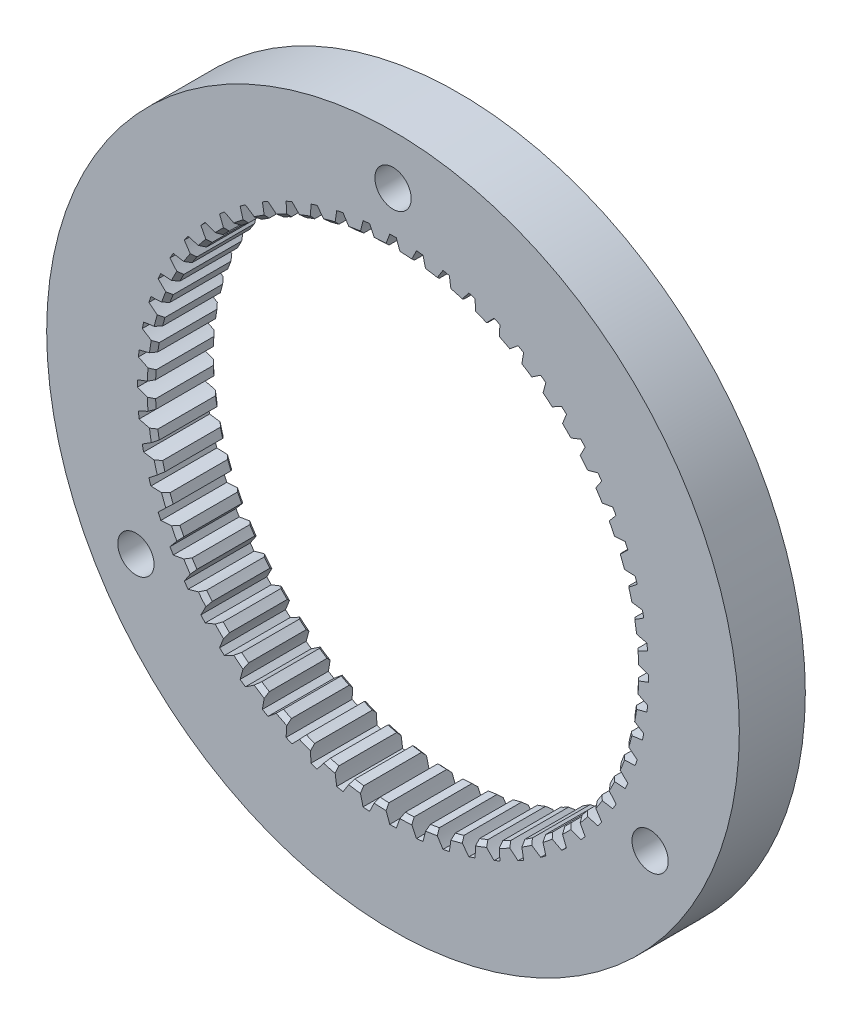
SolidWorks part; units mm, degrees
material "Plain Carbon Steel"
ref_plane "Front Plane" through (0, 0, 0) normal (0, 0, 1) x (1, 0, 0)
ref_plane "Top Plane" through (0, 0, 0) normal (0, 1, 0) x (1, 0, 0)
ref_plane "Right Plane" through (0, 0, 0) normal (1, 0, 0) x (0, 0, -1)
sketch "Model" plane through (0, 0, 0) normal (0, 0, 1) x (1, 0, 0)
  arc A1 (14.6125, -1.0371) -> (14.6408, -0.496) centre (0, 0) ccw
  arc A2 (15.3934, -1.8154) -> (15.4344, -1.4248) centre (0, 0) ccw
  arc A3 (14.424, -2.5588) -> (14.5088, -2.0237) centre (0, 0) ccw
  arc A4 (15.1193, -3.4145) -> (15.2009, -3.0303) centre (0, 0) ccw
  arc A5 (14.0775, -4.0525) -> (14.2178, -3.5292) centre (0, 0) ccw
  arc A6 (14.6796, -4.9762) -> (14.8009, -4.6026) centre (0, 0) ccw
  arc A7 (13.5768, -5.5018) -> (13.771, -4.996) centre (0, 0) ccw
  arc A8 (14.079, -6.4833) -> (14.2387, -6.1245) centre (0, 0) ccw
  arc A9 (12.9273, -6.8908) -> (13.1733, -6.4081) centre (0, 0) ccw
  arc A10 (13.3242, -7.9195) -> (13.5205, -7.5793) centre (0, 0) ccw
  arc A11 (12.1362, -8.2044) -> (12.4313, -7.75) centre (0, 0) ccw
  arc A12 (12.4234, -9.2688) -> (12.6542, -8.9511) centre (0, 0) ccw
  arc A13 (11.2122, -9.428) -> (11.5531, -9.007) centre (0, 0) ccw
  arc A14 (11.3865, -10.5167) -> (11.6493, -10.2248) centre (0, 0) ccw
  arc A15 (10.1652, -10.5484) -> (10.5484, -10.1652) centre (0, 0) ccw
  arc A16 (10.2248, -11.6493) -> (10.5167, -11.3865) centre (0, 0) ccw
  arc A17 (9.007, -11.5531) -> (9.428, -11.2122) centre (0, 0) ccw
  arc A18 (8.9511, -12.6542) -> (9.2688, -12.4234) centre (0, 0) ccw
  arc A19 (7.75, -12.4313) -> (8.2044, -12.1362) centre (0, 0) ccw
  arc A20 (7.5793, -13.5205) -> (7.9195, -13.3242) centre (0, 0) ccw
  arc A21 (6.4081, -13.1733) -> (6.8908, -12.9273) centre (0, 0) ccw
  arc A22 (6.1245, -14.2387) -> (6.4833, -14.079) centre (0, 0) ccw
  arc A23 (4.996, -13.771) -> (5.5018, -13.5768) centre (0, 0) ccw
  arc A24 (4.6026, -14.8009) -> (4.9762, -14.6796) centre (0, 0) ccw
  arc A25 (3.5292, -14.2178) -> (4.0525, -14.0775) centre (0, 0) ccw
  arc A26 (3.0303, -15.2009) -> (3.4145, -15.1193) centre (0, 0) ccw
  arc A27 (2.0237, -14.5088) -> (2.5588, -14.424) centre (0, 0) ccw
  arc A28 (1.4248, -15.4344) -> (1.8154, -15.3934) centre (0, 0) ccw
  arc A29 (0.496, -14.6408) -> (1.0371, -14.6125) centre (0, 0) ccw
  arc A30 (-0.1964, -15.4988) -> (0.1964, -15.4988) centre (0, 0) ccw
  arc A31 (-1.0371, -14.6125) -> (-0.496, -14.6408) centre (0, 0) ccw
  arc A32 (-1.8154, -15.3934) -> (-1.4248, -15.4344) centre (0, 0) ccw
  arc A33 (-2.5588, -14.424) -> (-2.0237, -14.5088) centre (0, 0) ccw
  arc A34 (-3.4145, -15.1193) -> (-3.0303, -15.2009) centre (0, 0) ccw
  arc A35 (-4.0525, -14.0775) -> (-3.5292, -14.2178) centre (0, 0) ccw
  arc A36 (-4.9762, -14.6796) -> (-4.6026, -14.8009) centre (0, 0) ccw
  arc A37 (-5.5018, -13.5768) -> (-4.996, -13.771) centre (0, 0) ccw
  arc A38 (-6.4833, -14.079) -> (-6.1245, -14.2387) centre (0, 0) ccw
  arc A39 (-6.8908, -12.9273) -> (-6.4081, -13.1733) centre (0, 0) ccw
  arc A40 (-7.9195, -13.3242) -> (-7.5793, -13.5205) centre (0, 0) ccw
  arc A41 (-8.2044, -12.1362) -> (-7.75, -12.4313) centre (0, 0) ccw
  arc A42 (-9.2688, -12.4234) -> (-8.9511, -12.6542) centre (0, 0) ccw
  arc A43 (-9.428, -11.2122) -> (-9.007, -11.5531) centre (0, 0) ccw
  arc A44 (-10.5167, -11.3865) -> (-10.2248, -11.6493) centre (0, 0) ccw
  arc A45 (-10.5484, -10.1652) -> (-10.1652, -10.5484) centre (0, 0) ccw
  arc A46 (-11.6493, -10.2248) -> (-11.3865, -10.5167) centre (0, 0) ccw
  arc A47 (-11.5531, -9.007) -> (-11.2122, -9.428) centre (0, 0) ccw
  arc A48 (-12.6542, -8.9511) -> (-12.4234, -9.2688) centre (0, 0) ccw
  arc A49 (-12.4313, -7.75) -> (-12.1362, -8.2044) centre (0, 0) ccw
  arc A50 (-13.5205, -7.5793) -> (-13.3242, -7.9195) centre (0, 0) ccw
  arc A51 (-13.1733, -6.4081) -> (-12.9273, -6.8908) centre (0, 0) ccw
  arc A52 (-14.2387, -6.1245) -> (-14.079, -6.4833) centre (0, 0) ccw
  arc A53 (-13.771, -4.996) -> (-13.5768, -5.5018) centre (0, 0) ccw
  arc A54 (-14.8009, -4.6026) -> (-14.6796, -4.9762) centre (0, 0) ccw
  arc A55 (-14.2178, -3.5292) -> (-14.0775, -4.0525) centre (0, 0) ccw
  arc A56 (-15.2009, -3.0303) -> (-15.1193, -3.4145) centre (0, 0) ccw
  arc A57 (-14.5088, -2.0237) -> (-14.424, -2.5588) centre (0, 0) ccw
  arc A58 (-15.4344, -1.4248) -> (-15.3934, -1.8154) centre (0, 0) ccw
  arc A59 (-14.6408, -0.496) -> (-14.6125, -1.0371) centre (0, 0) ccw
  arc A60 (-15.4988, 0.1964) -> (-15.4988, -0.1964) centre (0, 0) ccw
  arc A61 (-14.6125, 1.0371) -> (-14.6408, 0.496) centre (0, 0) ccw
  arc A62 (-15.3934, 1.8154) -> (-15.4344, 1.4248) centre (0, 0) ccw
  arc A63 (-14.424, 2.5588) -> (-14.5088, 2.0237) centre (0, 0) ccw
  arc A64 (-15.1193, 3.4145) -> (-15.2009, 3.0303) centre (0, 0) ccw
  arc A65 (-14.0775, 4.0525) -> (-14.2178, 3.5292) centre (0, 0) ccw
  arc A66 (-14.6796, 4.9762) -> (-14.8009, 4.6026) centre (0, 0) ccw
  arc A67 (-13.5768, 5.5018) -> (-13.771, 4.996) centre (0, 0) ccw
  arc A68 (-14.079, 6.4833) -> (-14.2387, 6.1245) centre (0, 0) ccw
  arc A69 (-12.9273, 6.8908) -> (-13.1733, 6.4081) centre (0, 0) ccw
  arc A70 (-13.3242, 7.9195) -> (-13.5205, 7.5793) centre (0, 0) ccw
  arc A71 (-12.1362, 8.2044) -> (-12.4313, 7.75) centre (0, 0) ccw
  arc A72 (-12.4234, 9.2688) -> (-12.6542, 8.9511) centre (0, 0) ccw
  arc A73 (-11.2122, 9.428) -> (-11.5531, 9.007) centre (0, 0) ccw
  arc A74 (-11.3865, 10.5167) -> (-11.6493, 10.2248) centre (0, 0) ccw
  arc A75 (-10.1652, 10.5484) -> (-10.5484, 10.1652) centre (0, 0) ccw
  arc A76 (-10.2248, 11.6493) -> (-10.5167, 11.3865) centre (0, 0) ccw
  arc A77 (-9.007, 11.5531) -> (-9.428, 11.2122) centre (0, 0) ccw
  arc A78 (-8.9511, 12.6542) -> (-9.2688, 12.4234) centre (0, 0) ccw
  arc A79 (-7.75, 12.4313) -> (-8.2044, 12.1362) centre (0, 0) ccw
  arc A80 (-7.5793, 13.5205) -> (-7.9195, 13.3242) centre (0, 0) ccw
  arc A81 (-6.4081, 13.1733) -> (-6.8908, 12.9273) centre (0, 0) ccw
  arc A82 (-6.1245, 14.2387) -> (-6.4833, 14.079) centre (0, 0) ccw
  arc A83 (-4.996, 13.771) -> (-5.5018, 13.5768) centre (0, 0) ccw
  arc A84 (-4.6026, 14.8009) -> (-4.9762, 14.6796) centre (0, 0) ccw
  arc A85 (-3.5292, 14.2178) -> (-4.0525, 14.0775) centre (0, 0) ccw
  arc A86 (-3.0303, 15.2009) -> (-3.4145, 15.1193) centre (0, 0) ccw
  arc A87 (-2.0237, 14.5088) -> (-2.5588, 14.424) centre (0, 0) ccw
  arc A88 (-1.4248, 15.4344) -> (-1.8154, 15.3934) centre (0, 0) ccw
  arc A89 (-0.496, 14.6408) -> (-1.0371, 14.6125) centre (0, 0) ccw
  arc A90 (0.1964, 15.4988) -> (-0.1964, 15.4988) centre (0, 0) ccw
  arc A91 (1.0371, 14.6125) -> (0.496, 14.6408) centre (0, 0) ccw
  arc A92 (1.8154, 15.3934) -> (1.4248, 15.4344) centre (0, 0) ccw
  arc A93 (2.5588, 14.424) -> (2.0237, 14.5088) centre (0, 0) ccw
  arc A94 (3.4145, 15.1193) -> (3.0303, 15.2009) centre (0, 0) ccw
  arc A95 (4.0525, 14.0775) -> (3.5292, 14.2178) centre (0, 0) ccw
  arc A96 (4.9762, 14.6796) -> (4.6026, 14.8009) centre (0, 0) ccw
  arc A97 (5.5018, 13.5768) -> (4.996, 13.771) centre (0, 0) ccw
  arc A98 (6.4833, 14.079) -> (6.1245, 14.2387) centre (0, 0) ccw
  arc A99 (6.8908, 12.9273) -> (6.4081, 13.1733) centre (0, 0) ccw
  arc A100 (7.9195, 13.3242) -> (7.5793, 13.5205) centre (0, 0) ccw
  arc A101 (8.2044, 12.1362) -> (7.75, 12.4313) centre (0, 0) ccw
  arc A102 (9.2688, 12.4234) -> (8.9511, 12.6542) centre (0, 0) ccw
  arc A103 (9.428, 11.2122) -> (9.007, 11.5531) centre (0, 0) ccw
  arc A104 (10.5167, 11.3865) -> (10.2248, 11.6493) centre (0, 0) ccw
  arc A105 (10.5484, 10.1652) -> (10.1652, 10.5484) centre (0, 0) ccw
  arc A106 (11.6493, 10.2248) -> (11.3865, 10.5167) centre (0, 0) ccw
  arc A107 (11.5531, 9.007) -> (11.2122, 9.428) centre (0, 0) ccw
  arc A108 (12.6542, 8.9511) -> (12.4234, 9.2688) centre (0, 0) ccw
  arc A109 (12.4313, 7.75) -> (12.1362, 8.2044) centre (0, 0) ccw
  arc A110 (13.5205, 7.5793) -> (13.3242, 7.9195) centre (0, 0) ccw
  arc A111 (13.1733, 6.4081) -> (12.9273, 6.8908) centre (0, 0) ccw
  arc A112 (14.2387, 6.1245) -> (14.079, 6.4833) centre (0, 0) ccw
  arc A113 (13.771, 4.996) -> (13.5768, 5.5018) centre (0, 0) ccw
  arc A114 (14.8009, 4.6026) -> (14.6796, 4.9762) centre (0, 0) ccw
  arc A115 (14.2178, 3.5292) -> (14.0775, 4.0525) centre (0, 0) ccw
  arc A116 (15.2009, 3.0303) -> (15.1193, 3.4145) centre (0, 0) ccw
  arc A117 (14.5088, 2.0237) -> (14.424, 2.5588) centre (0, 0) ccw
  arc A118 (15.4344, 1.4248) -> (15.3934, 1.8154) centre (0, 0) ccw
  arc A119 (14.6408, 0.496) -> (14.6125, 1.0371) centre (0, 0) ccw
  arc A120 (15.4988, -0.1964) -> (15.4988, 0.1964) centre (0, 0) ccw
  circle A121 centre (0, 0) radius 21
  spline S0 degree 3 poles (14.6125, -1.0371) (15.0016, -1.1948) (15.2065, -1.2939) (15.4344, -1.4248) knots 0 0 0 0 1 1 1 1
  spline S1 degree 3 poles (15.3934, -1.8154) (15.1432, -1.8959) (14.9222, -1.9503) (14.5088, -2.0237) knots 0 0 0 0 1 1 1 1
  spline S2 degree 3 poles (14.424, -2.5588) (14.7945, -2.7564) (14.988, -2.8764) (15.2009, -3.0303) knots 0 0 0 0 1 1 1 1
  spline S3 degree 3 poles (15.1193, -3.4145) (14.8621, -3.4685) (14.6366, -3.4994) (14.2178, -3.5292) knots 0 0 0 0 1 1 1 1
  spline S4 degree 3 poles (14.0775, -4.0525) (14.4253, -4.2877) (14.6052, -4.4273) (14.8009, -4.6026) knots 0 0 0 0 1 1 1 1
  spline S5 degree 3 poles (14.6796, -4.9762) (14.4181, -5.003) (14.1906, -5.0102) (13.771, -4.996) knots 0 0 0 0 1 1 1 1
  spline S6 degree 3 poles (13.5768, -5.5018) (13.8981, -5.7721) (14.0624, -5.9297) (14.2387, -6.1245) knots 0 0 0 0 1 1 1 1
  spline S7 degree 3 poles (14.079, -6.4833) (13.8162, -6.4827) (13.5892, -6.466) (13.1733, -6.4081) knots 0 0 0 0 1 1 1 1
  spline S8 degree 3 poles (12.9273, -6.8908) (13.2186, -7.1932) (13.3655, -7.3671) (13.5205, -7.5793) knots 0 0 0 0 1 1 1 1
  spline S9 degree 3 poles (13.3242, -7.9195) (13.0629, -7.8913) (12.8388, -7.8511) (12.4313, -7.75) knots 0 0 0 0 1 1 1 1
  spline S10 degree 3 poles (12.1362, -8.2044) (12.3943, -8.5355) (12.5223, -8.7238) (12.6542, -8.9511) knots 0 0 0 0 1 1 1 1
  spline S11 degree 3 poles (12.4234, -9.2688) (12.1665, -9.2136) (11.9478, -9.1501) (11.5531, -9.007) knots 0 0 0 0 1 1 1 1
  spline S12 degree 3 poles (11.2122, -9.428) (11.4342, -9.7844) (11.5418, -9.985) (11.6493, -10.2248) knots 0 0 0 0 1 1 1 1
  spline S13 degree 3 poles (11.3865, -10.5167) (11.1367, -10.4348) (10.926, -10.3489) (10.5484, -10.1652) knots 0 0 0 0 1 1 1 1
  spline S14 degree 3 poles (10.1652, -10.5484) (10.3489, -10.926) (10.4348, -11.1367) (10.5167, -11.3865) knots 0 0 0 0 1 1 1 1
  spline S15 degree 3 poles (10.2248, -11.6493) (9.985, -11.5418) (9.7844, -11.4342) (9.428, -11.2122) knots 0 0 0 0 1 1 1 1
  spline S16 degree 3 poles (9.007, -11.5531) (9.1501, -11.9478) (9.2136, -12.1665) (9.2688, -12.4234) knots 0 0 0 0 1 1 1 1
  spline S17 degree 3 poles (8.9511, -12.6542) (8.7238, -12.5223) (8.5355, -12.3943) (8.2044, -12.1362) knots 0 0 0 0 1 1 1 1
  spline S18 degree 3 poles (7.75, -12.4313) (7.8511, -12.8388) (7.8913, -13.0629) (7.9195, -13.3242) knots 0 0 0 0 1 1 1 1
  spline S19 degree 3 poles (7.5793, -13.5205) (7.3671, -13.3655) (7.1932, -13.2186) (6.8908, -12.9273) knots 0 0 0 0 1 1 1 1
  spline S20 degree 3 poles (6.4081, -13.1733) (6.466, -13.5892) (6.4827, -13.8162) (6.4833, -14.079) knots 0 0 0 0 1 1 1 1
  spline S21 degree 3 poles (6.1245, -14.2387) (5.9297, -14.0624) (5.7721, -13.8981) (5.5018, -13.5768) knots 0 0 0 0 1 1 1 1
  spline S22 degree 3 poles (4.996, -13.771) (5.0102, -14.1906) (5.003, -14.4181) (4.9762, -14.6796) knots 0 0 0 0 1 1 1 1
  spline S23 degree 3 poles (4.6026, -14.8009) (4.4273, -14.6052) (4.2877, -14.4253) (4.0525, -14.0775) knots 0 0 0 0 1 1 1 1
  spline S24 degree 3 poles (3.5292, -14.2178) (3.4994, -14.6366) (3.4685, -14.8621) (3.4145, -15.1193) knots 0 0 0 0 1 1 1 1
  spline S25 degree 3 poles (3.0303, -15.2009) (2.8764, -14.988) (2.7564, -14.7945) (2.5588, -14.424) knots 0 0 0 0 1 1 1 1
  spline S26 degree 3 poles (2.0237, -14.5088) (1.9503, -14.9222) (1.8959, -15.1432) (1.8154, -15.3934) knots 0 0 0 0 1 1 1 1
  spline S27 degree 3 poles (1.4248, -15.4344) (1.2939, -15.2065) (1.1948, -15.0016) (1.0371, -14.6125) knots 0 0 0 0 1 1 1 1
  spline S28 degree 3 poles (0.496, -14.6408) (0.3798, -15.0443) (0.3027, -15.2585) (0.1964, -15.4988) knots 0 0 0 0 1 1 1 1
  spline S29 degree 3 poles (-0.1964, -15.4988) (-0.3027, -15.2585) (-0.3798, -15.0443) (-0.496, -14.6408) knots 0 0 0 0 1 1 1 1
  spline S30 degree 3 poles (-1.0371, -14.6125) (-1.1948, -15.0016) (-1.2939, -15.2065) (-1.4248, -15.4344) knots 0 0 0 0 1 1 1 1
  spline S31 degree 3 poles (-1.8154, -15.3934) (-1.8959, -15.1432) (-1.9503, -14.9222) (-2.0237, -14.5088) knots 0 0 0 0 1 1 1 1
  spline S32 degree 3 poles (-2.5588, -14.424) (-2.7564, -14.7945) (-2.8764, -14.988) (-3.0303, -15.2009) knots 0 0 0 0 1 1 1 1
  spline S33 degree 3 poles (-3.4145, -15.1193) (-3.4685, -14.8621) (-3.4994, -14.6366) (-3.5292, -14.2178) knots 0 0 0 0 1 1 1 1
  spline S34 degree 3 poles (-4.0525, -14.0775) (-4.2877, -14.4253) (-4.4273, -14.6052) (-4.6026, -14.8009) knots 0 0 0 0 1 1 1 1
  spline S35 degree 3 poles (-4.9762, -14.6796) (-5.003, -14.4181) (-5.0102, -14.1906) (-4.996, -13.771) knots 0 0 0 0 1 1 1 1
  spline S36 degree 3 poles (-5.5018, -13.5768) (-5.7721, -13.8981) (-5.9297, -14.0624) (-6.1245, -14.2387) knots 0 0 0 0 1 1 1 1
  spline S37 degree 3 poles (-6.4833, -14.079) (-6.4827, -13.8162) (-6.466, -13.5892) (-6.4081, -13.1733) knots 0 0 0 0 1 1 1 1
  spline S38 degree 3 poles (-6.8908, -12.9273) (-7.1932, -13.2186) (-7.3671, -13.3655) (-7.5793, -13.5205) knots 0 0 0 0 1 1 1 1
  spline S39 degree 3 poles (-7.9195, -13.3242) (-7.8913, -13.0629) (-7.8511, -12.8388) (-7.75, -12.4313) knots 0 0 0 0 1 1 1 1
  spline S40 degree 3 poles (-8.2044, -12.1362) (-8.5355, -12.3943) (-8.7238, -12.5223) (-8.9511, -12.6542) knots 0 0 0 0 1 1 1 1
  spline S41 degree 3 poles (-9.2688, -12.4234) (-9.2136, -12.1665) (-9.1501, -11.9478) (-9.007, -11.5531) knots 0 0 0 0 1 1 1 1
  spline S42 degree 3 poles (-9.428, -11.2122) (-9.7844, -11.4342) (-9.985, -11.5418) (-10.2248, -11.6493) knots 0 0 0 0 1 1 1 1
  spline S43 degree 3 poles (-10.5167, -11.3865) (-10.4348, -11.1367) (-10.3489, -10.926) (-10.1652, -10.5484) knots 0 0 0 0 1 1 1 1
  spline S44 degree 3 poles (-10.5484, -10.1652) (-10.926, -10.3489) (-11.1367, -10.4348) (-11.3865, -10.5167) knots 0 0 0 0 1 1 1 1
  spline S45 degree 3 poles (-11.6493, -10.2248) (-11.5418, -9.985) (-11.4342, -9.7844) (-11.2122, -9.428) knots 0 0 0 0 1 1 1 1
  spline S46 degree 3 poles (-11.5531, -9.007) (-11.9478, -9.1501) (-12.1665, -9.2136) (-12.4234, -9.2688) knots 0 0 0 0 1 1 1 1
  spline S47 degree 3 poles (-12.6542, -8.9511) (-12.5223, -8.7238) (-12.3943, -8.5355) (-12.1362, -8.2044) knots 0 0 0 0 1 1 1 1
  spline S48 degree 3 poles (-12.4313, -7.75) (-12.8388, -7.8511) (-13.0629, -7.8913) (-13.3242, -7.9195) knots 0 0 0 0 1 1 1 1
  spline S49 degree 3 poles (-13.5205, -7.5793) (-13.3655, -7.3671) (-13.2186, -7.1932) (-12.9273, -6.8908) knots 0 0 0 0 1 1 1 1
  spline S50 degree 3 poles (-13.1733, -6.4081) (-13.5892, -6.466) (-13.8162, -6.4827) (-14.079, -6.4833) knots 0 0 0 0 1 1 1 1
  spline S51 degree 3 poles (-14.2387, -6.1245) (-14.0624, -5.9297) (-13.8981, -5.7721) (-13.5768, -5.5018) knots 0 0 0 0 1 1 1 1
  spline S52 degree 3 poles (-13.771, -4.996) (-14.1906, -5.0102) (-14.4181, -5.003) (-14.6796, -4.9762) knots 0 0 0 0 1 1 1 1
  spline S53 degree 3 poles (-14.8009, -4.6026) (-14.6052, -4.4273) (-14.4253, -4.2877) (-14.0775, -4.0525) knots 0 0 0 0 1 1 1 1
  spline S54 degree 3 poles (-14.2178, -3.5292) (-14.6366, -3.4994) (-14.8621, -3.4685) (-15.1193, -3.4145) knots 0 0 0 0 1 1 1 1
  spline S55 degree 3 poles (-15.2009, -3.0303) (-14.988, -2.8764) (-14.7945, -2.7564) (-14.424, -2.5588) knots 0 0 0 0 1 1 1 1
  spline S56 degree 3 poles (-14.5088, -2.0237) (-14.9222, -1.9503) (-15.1432, -1.8959) (-15.3934, -1.8154) knots 0 0 0 0 1 1 1 1
  spline S57 degree 3 poles (-15.4344, -1.4248) (-15.2065, -1.2939) (-15.0016, -1.1948) (-14.6125, -1.0371) knots 0 0 0 0 1 1 1 1
  spline S58 degree 3 poles (-14.6408, -0.496) (-15.0443, -0.3798) (-15.2585, -0.3027) (-15.4988, -0.1964) knots 0 0 0 0 1 1 1 1
  spline S59 degree 3 poles (-15.4988, 0.1964) (-15.2585, 0.3027) (-15.0443, 0.3798) (-14.6408, 0.496) knots 0 0 0 0 1 1 1 1
  spline S60 degree 3 poles (-14.6125, 1.0371) (-15.0016, 1.1948) (-15.2065, 1.2939) (-15.4344, 1.4248) knots 0 0 0 0 1 1 1 1
  spline S61 degree 3 poles (-15.3934, 1.8154) (-15.1432, 1.8959) (-14.9222, 1.9503) (-14.5088, 2.0237) knots 0 0 0 0 1 1 1 1
  spline S62 degree 3 poles (-14.424, 2.5588) (-14.7945, 2.7564) (-14.988, 2.8764) (-15.2009, 3.0303) knots 0 0 0 0 1 1 1 1
  spline S63 degree 3 poles (-15.1193, 3.4145) (-14.8621, 3.4685) (-14.6366, 3.4994) (-14.2178, 3.5292) knots 0 0 0 0 1 1 1 1
  spline S64 degree 3 poles (-14.0775, 4.0525) (-14.4253, 4.2877) (-14.6052, 4.4273) (-14.8009, 4.6026) knots 0 0 0 0 1 1 1 1
  spline S65 degree 3 poles (-14.6796, 4.9762) (-14.4181, 5.003) (-14.1906, 5.0102) (-13.771, 4.996) knots 0 0 0 0 1 1 1 1
  spline S66 degree 3 poles (-13.5768, 5.5018) (-13.8981, 5.7721) (-14.0624, 5.9297) (-14.2387, 6.1245) knots 0 0 0 0 1 1 1 1
  spline S67 degree 3 poles (-14.079, 6.4833) (-13.8162, 6.4827) (-13.5892, 6.466) (-13.1733, 6.4081) knots 0 0 0 0 1 1 1 1
  spline S68 degree 3 poles (-12.9273, 6.8908) (-13.2186, 7.1932) (-13.3655, 7.3671) (-13.5205, 7.5793) knots 0 0 0 0 1 1 1 1
  spline S69 degree 3 poles (-13.3242, 7.9195) (-13.0629, 7.8913) (-12.8388, 7.8511) (-12.4313, 7.75) knots 0 0 0 0 1 1 1 1
  spline S70 degree 3 poles (-12.1362, 8.2044) (-12.3943, 8.5355) (-12.5223, 8.7238) (-12.6542, 8.9511) knots 0 0 0 0 1 1 1 1
  spline S71 degree 3 poles (-12.4234, 9.2688) (-12.1665, 9.2136) (-11.9478, 9.1501) (-11.5531, 9.007) knots 0 0 0 0 1 1 1 1
  spline S72 degree 3 poles (-11.2122, 9.428) (-11.4342, 9.7844) (-11.5418, 9.985) (-11.6493, 10.2248) knots 0 0 0 0 1 1 1 1
  spline S73 degree 3 poles (-11.3865, 10.5167) (-11.1367, 10.4348) (-10.926, 10.3489) (-10.5484, 10.1652) knots 0 0 0 0 1 1 1 1
  spline S74 degree 3 poles (-10.1652, 10.5484) (-10.3489, 10.926) (-10.4348, 11.1367) (-10.5167, 11.3865) knots 0 0 0 0 1 1 1 1
  spline S75 degree 3 poles (-10.2248, 11.6493) (-9.985, 11.5418) (-9.7844, 11.4342) (-9.428, 11.2122) knots 0 0 0 0 1 1 1 1
  spline S76 degree 3 poles (-9.007, 11.5531) (-9.1501, 11.9478) (-9.2136, 12.1665) (-9.2688, 12.4234) knots 0 0 0 0 1 1 1 1
  spline S77 degree 3 poles (-8.9511, 12.6542) (-8.7238, 12.5223) (-8.5355, 12.3943) (-8.2044, 12.1362) knots 0 0 0 0 1 1 1 1
  spline S78 degree 3 poles (-7.75, 12.4313) (-7.8511, 12.8388) (-7.8913, 13.0629) (-7.9195, 13.3242) knots 0 0 0 0 1 1 1 1
  spline S79 degree 3 poles (-7.5793, 13.5205) (-7.3671, 13.3655) (-7.1932, 13.2186) (-6.8908, 12.9273) knots 0 0 0 0 1 1 1 1
  spline S80 degree 3 poles (-6.4081, 13.1733) (-6.466, 13.5892) (-6.4827, 13.8162) (-6.4833, 14.079) knots 0 0 0 0 1 1 1 1
  spline S81 degree 3 poles (-6.1245, 14.2387) (-5.9297, 14.0624) (-5.7721, 13.8981) (-5.5018, 13.5768) knots 0 0 0 0 1 1 1 1
  spline S82 degree 3 poles (-4.996, 13.771) (-5.0102, 14.1906) (-5.003, 14.4181) (-4.9762, 14.6796) knots 0 0 0 0 1 1 1 1
  spline S83 degree 3 poles (-4.6026, 14.8009) (-4.4273, 14.6052) (-4.2877, 14.4253) (-4.0525, 14.0775) knots 0 0 0 0 1 1 1 1
  spline S84 degree 3 poles (-3.5292, 14.2178) (-3.4994, 14.6366) (-3.4685, 14.8621) (-3.4145, 15.1193) knots 0 0 0 0 1 1 1 1
  spline S85 degree 3 poles (-3.0303, 15.2009) (-2.8764, 14.988) (-2.7564, 14.7945) (-2.5588, 14.424) knots 0 0 0 0 1 1 1 1
  spline S86 degree 3 poles (-2.0237, 14.5088) (-1.9503, 14.9222) (-1.8959, 15.1432) (-1.8154, 15.3934) knots 0 0 0 0 1 1 1 1
  spline S87 degree 3 poles (-1.4248, 15.4344) (-1.2939, 15.2065) (-1.1948, 15.0016) (-1.0371, 14.6125) knots 0 0 0 0 1 1 1 1
  spline S88 degree 3 poles (-0.496, 14.6408) (-0.3798, 15.0443) (-0.3027, 15.2585) (-0.1964, 15.4988) knots 0 0 0 0 1 1 1 1
  spline S89 degree 3 poles (0.1964, 15.4988) (0.3027, 15.2585) (0.3798, 15.0443) (0.496, 14.6408) knots 0 0 0 0 1 1 1 1
  spline S90 degree 3 poles (1.0371, 14.6125) (1.1948, 15.0016) (1.2939, 15.2065) (1.4248, 15.4344) knots 0 0 0 0 1 1 1 1
  spline S91 degree 3 poles (1.8154, 15.3934) (1.8959, 15.1432) (1.9503, 14.9222) (2.0237, 14.5088) knots 0 0 0 0 1 1 1 1
  spline S92 degree 3 poles (2.5588, 14.424) (2.7564, 14.7945) (2.8764, 14.988) (3.0303, 15.2009) knots 0 0 0 0 1 1 1 1
  spline S93 degree 3 poles (3.4145, 15.1193) (3.4685, 14.8621) (3.4994, 14.6366) (3.5292, 14.2178) knots 0 0 0 0 1 1 1 1
  spline S94 degree 3 poles (4.0525, 14.0775) (4.2877, 14.4253) (4.4273, 14.6052) (4.6026, 14.8009) knots 0 0 0 0 1 1 1 1
  spline S95 degree 3 poles (4.9762, 14.6796) (5.003, 14.4181) (5.0102, 14.1906) (4.996, 13.771) knots 0 0 0 0 1 1 1 1
  spline S96 degree 3 poles (5.5018, 13.5768) (5.7721, 13.8981) (5.9297, 14.0624) (6.1245, 14.2387) knots 0 0 0 0 1 1 1 1
  spline S97 degree 3 poles (6.4833, 14.079) (6.4827, 13.8162) (6.466, 13.5892) (6.4081, 13.1733) knots 0 0 0 0 1 1 1 1
  spline S98 degree 3 poles (6.8908, 12.9273) (7.1932, 13.2186) (7.3671, 13.3655) (7.5793, 13.5205) knots 0 0 0 0 1 1 1 1
  spline S99 degree 3 poles (7.9195, 13.3242) (7.8913, 13.0629) (7.8511, 12.8388) (7.75, 12.4313) knots 0 0 0 0 1 1 1 1
  spline S100 degree 3 poles (8.2044, 12.1362) (8.5355, 12.3943) (8.7238, 12.5223) (8.9511, 12.6542) knots 0 0 0 0 1 1 1 1
  spline S101 degree 3 poles (9.2688, 12.4234) (9.2136, 12.1665) (9.1501, 11.9478) (9.007, 11.5531) knots 0 0 0 0 1 1 1 1
  spline S102 degree 3 poles (9.428, 11.2122) (9.7844, 11.4342) (9.985, 11.5418) (10.2248, 11.6493) knots 0 0 0 0 1 1 1 1
  spline S103 degree 3 poles (10.5167, 11.3865) (10.4348, 11.1367) (10.3489, 10.926) (10.1652, 10.5484) knots 0 0 0 0 1 1 1 1
  spline S104 degree 3 poles (10.5484, 10.1652) (10.926, 10.3489) (11.1367, 10.4348) (11.3865, 10.5167) knots 0 0 0 0 1 1 1 1
  spline S105 degree 3 poles (11.6493, 10.2248) (11.5418, 9.985) (11.4342, 9.7844) (11.2122, 9.428) knots 0 0 0 0 1 1 1 1
  spline S106 degree 3 poles (11.5531, 9.007) (11.9478, 9.1501) (12.1665, 9.2136) (12.4234, 9.2688) knots 0 0 0 0 1 1 1 1
  spline S107 degree 3 poles (12.6542, 8.9511) (12.5223, 8.7238) (12.3943, 8.5355) (12.1362, 8.2044) knots 0 0 0 0 1 1 1 1
  spline S108 degree 3 poles (12.4313, 7.75) (12.8388, 7.8511) (13.0629, 7.8913) (13.3242, 7.9195) knots 0 0 0 0 1 1 1 1
  spline S109 degree 3 poles (13.5205, 7.5793) (13.3655, 7.3671) (13.2186, 7.1932) (12.9273, 6.8908) knots 0 0 0 0 1 1 1 1
  spline S110 degree 3 poles (13.1733, 6.4081) (13.5892, 6.466) (13.8162, 6.4827) (14.079, 6.4833) knots 0 0 0 0 1 1 1 1
  spline S111 degree 3 poles (14.2387, 6.1245) (14.0624, 5.9297) (13.8981, 5.7721) (13.5768, 5.5018) knots 0 0 0 0 1 1 1 1
  spline S112 degree 3 poles (13.771, 4.996) (14.1906, 5.0102) (14.4181, 5.003) (14.6796, 4.9762) knots 0 0 0 0 1 1 1 1
  spline S113 degree 3 poles (14.8009, 4.6026) (14.6052, 4.4273) (14.4253, 4.2877) (14.0775, 4.0525) knots 0 0 0 0 1 1 1 1
  spline S114 degree 3 poles (14.2178, 3.5292) (14.6366, 3.4994) (14.8621, 3.4685) (15.1193, 3.4145) knots 0 0 0 0 1 1 1 1
  spline S115 degree 3 poles (15.2009, 3.0303) (14.988, 2.8764) (14.7945, 2.7564) (14.424, 2.5588) knots 0 0 0 0 1 1 1 1
  spline S116 degree 3 poles (14.5088, 2.0237) (14.9222, 1.9503) (15.1432, 1.8959) (15.3934, 1.8154) knots 0 0 0 0 1 1 1 1
  spline S117 degree 3 poles (15.4344, 1.4248) (15.2065, 1.2939) (15.0016, 1.1948) (14.6125, 1.0371) knots 0 0 0 0 1 1 1 1
  spline S118 degree 3 poles (14.6408, 0.496) (15.0443, 0.3798) (15.2585, 0.3027) (15.4988, 0.1964) knots 0 0 0 0 1 1 1 1
  spline S119 degree 3 poles (15.4988, -0.1964) (15.2585, -0.3027) (15.0443, -0.3798) (14.6408, -0.496) knots 0 0 0 0 1 1 1 1
  dimension "D1" = 42
extrude "Boss-Extrude1" add sketch "Model" along normal blind 4
hole_wizard "M2 Clearance Hole1" positions "Sketch2" profile "Sketch3" hole size "M2" standard "ANSI Metric"
sketch "Sketch2" plane through (0, 0, 0) normal (0, 0, -1) x (-1, 0, 0)
  circle A0 centre (0, 0) radius 18 construction
  point P11 (0, 18)
  point P43 (15.5885, -9)
  point P45 (-15.5885, -9)
  point P50 (15.5885, 9)
  point P52 (-15.5885, 9)
  point P63 (0, -18)
  dimension "D2" = 36
  dimension "D1" = 6
sketch "Sketch3" plane through (0, 18, 0) normal (1, 0, 0) x (0, 1, 0)
  line L0 (0, 0) -> (0, 4)
  line L1 (0, 4) -> (1.1, 4)
  line L2 (1.1, 4) -> (1.1, 0.9)
  line L3 (1.1, 0.9) -> (2, 0)
  line L5 (2, 0) -> (0, 0)
  line L6 (-1.1, 0.9) -> (-2, 0) construction
  line L11 (0, -6.35) -> (0, 107.95) construction
  dimension "Thru Hole Dia." = 2.2
  dimension "Thru Hole Depth" = 4
  dimension "Near C'Sink Dia." = 4
  dimension "Near C'Sink Angle" = 90
chamfer "Chamfer1" distance 0.25 angle 45 60 edges at (12.2859, -7.9785, 0) (13.0526, -6.6506, 0) (13.6762, -5.2498, 0) (14.1501, -3.7915, 0) (14.4689, -2.2916, 0) (14.6292, -0.7667, 0) (14.6292, 0.7667, 0) (14.4689, 2.2916, 0) (14.1501, 3.7915, 0) (11.3846, -9.2191, 0) (10.3586, -10.3586, 0) (9.2191, -11.3846, 0) (6.6506, -13.0526, 0) (7.9785, -12.2859, 0) (5.2498, -13.6762, 0) (3.7915, -14.1501, 0) (2.2916, -14.4689, 0) (0.7667, -14.6292, 0) (-0.7667, -14.6292, 0) (-2.2916, -14.4689, 0) (-3.7915, -14.1501, 0) (-5.2498, -13.6762, 0) (-6.6506, -13.0526, 0) (-7.9785, -12.2859, 0) (13.6762, 5.2498, 0) (13.0526, 6.6506, 0) (-14.4689, 2.2916, 0) (-14.1501, 3.7915, 0) (-13.6762, 5.2498, 0) (-13.0526, 6.6506, 0) (-12.2859, 7.9785, 0) (-11.3846, 9.2191, 0) (-10.3586, 10.3586, 0) (-14.6292, 0.7667, 0) (-9.2191, -11.3846, 0) (-10.3586, -10.3586, 0) (-14.6292, -0.7667, 0) (-14.4689, -2.2916, 0) (-14.1501, -3.7915, 0) (-13.6762, -5.2498, 0) (-13.0526, -6.6506, 0) (-12.2859, -7.9785, 0) (-11.3846, -9.2191, 0) (-9.2191, 11.3846, 0) (-7.9785, 12.2859, 0) (-6.6506, 13.0526, 0) (-5.2498, 13.6762, 0) (-3.7915, 14.1501, 0) (-2.2916, 14.4689, 0) (-0.7667, 14.6292, 0) (0.7667, 14.6292, 0) (2.2916, 14.4689, 0) (3.7915, 14.1501, 0) (5.2498, 13.6762, 0) (6.6506, 13.0526, 0) (7.9785, 12.2859, 0) (9.2191, 11.3846, 0) (10.3586, 10.3586, 0) (11.3846, 9.2191, 0) (12.2859, 7.9785, 0)
chamfer "Chamfer2" distance 0.25 angle 45 60 edges at (-7.9785, -12.2859, 4) (-9.2191, -11.3846, 4) (-10.3586, -10.3586, 4) (-11.3846, -9.2191, 4) (-12.2859, -7.9785, 4) (-13.0526, -6.6506, 4) (-13.6762, -5.2498, 4) (-14.1501, -3.7915, 4) (-14.4689, -2.2916, 4) (-6.6506, -13.0526, 4) (-5.2498, -13.6762, 4) (-3.7915, -14.1501, 4) (-2.2916, -14.4689, 4) (-0.7667, -14.6292, 4) (0.7667, -14.6292, 4) (2.2916, -14.4689, 4) (3.7915, -14.1501, 4) (5.2498, -13.6762, 4) (6.6506, -13.0526, 4) (7.9785, -12.2859, 4) (9.2191, -11.3846, 4) (10.3586, -10.3586, 4) (11.3846, -9.2191, 4) (12.2859, -7.9785, 4) (13.0526, -6.6506, 4) (13.6762, -5.2498, 4) (14.1501, -3.7915, 4) (14.4689, -2.2916, 4) (14.6292, -0.7667, 4) (14.6292, 0.7667, 4) (14.4689, 2.2916, 4) (14.1501, 3.7915, 4) (13.6762, 5.2498, 4) (13.0526, 6.6506, 4) (12.2859, 7.9785, 4) (11.3846, 9.2191, 4) (10.3586, 10.3586, 4) (-14.6292, -0.7667, 4) (-14.6292, 0.7667, 4) (-14.4689, 2.2916, 4) (-14.1501, 3.7915, 4) (-13.6762, 5.2498, 4) (9.2191, 11.3846, 4) (7.9785, 12.2859, 4) (6.6506, 13.0526, 4) (5.2498, 13.6762, 4) (-13.0526, 6.6506, 4) (-12.2859, 7.9785, 4) (-11.3846, 9.2191, 4) (-10.3586, 10.3586, 4) (-9.2191, 11.3846, 4) (-7.9785, 12.2859, 4) (3.7915, 14.1501, 4) (2.2916, 14.4689, 4) (0.7667, 14.6292, 4) (-0.7667, 14.6292, 4) (-2.2916, 14.4689, 4) (-3.7915, 14.1501, 4) (-5.2498, 13.6762, 4) (-6.6506, 13.0526, 4)
